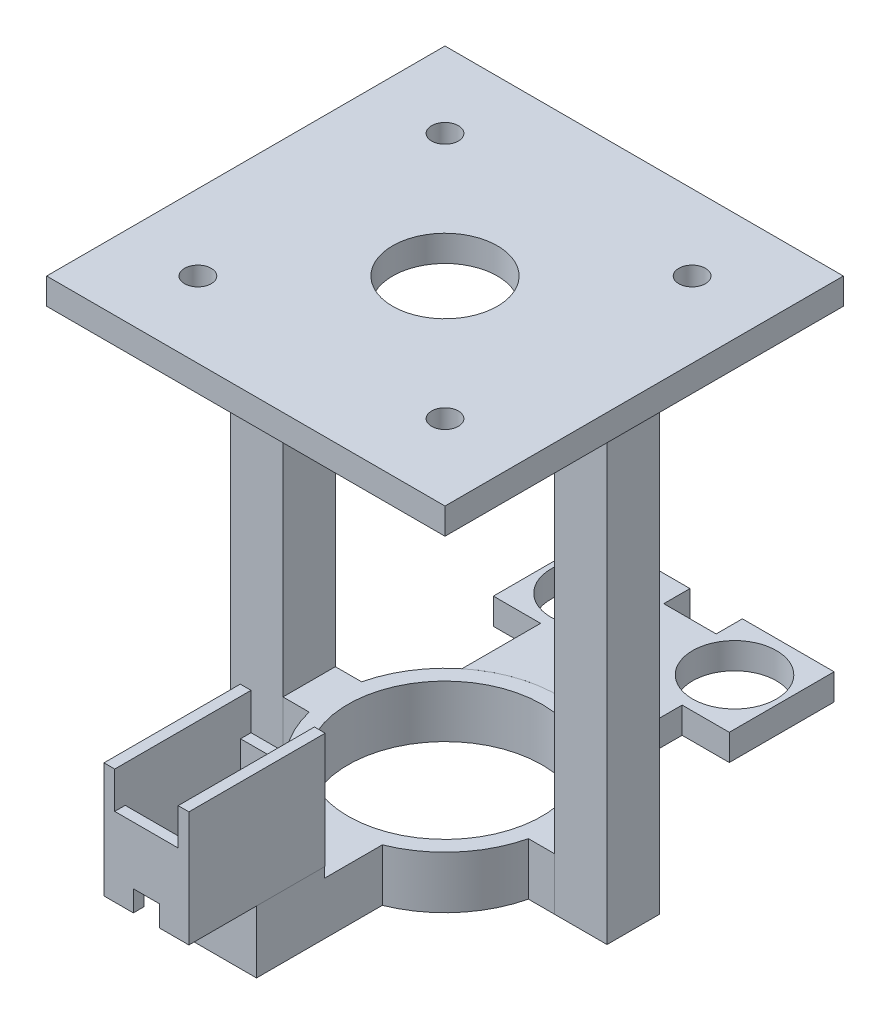
SolidWorks part; units mm, degrees
ref_plane "Front Plane" through (0, 0, 0) normal (0, 0, 1) x (1, 0, 0)
ref_plane "Top Plane" through (0, 0, 0) normal (0, 1, 0) x (1, 0, 0)
ref_plane "Right Plane" through (0, 0, 0) normal (1, 0, 0) x (0, 0, -1)
sketch "Sketch2" plane through (0, 0, 0) normal (0, 1, 0) x (1, 0, 0)
  line L0 (0, 18.5) -> (0, -18.5) construction
  line L1 (-18.5, 0) -> (18.5, 0) construction
  line L2 (0, -5) -> (0, 5) construction
  line L3 (-20.9105, 5) -> (-35.9105, 5)
  line L4 (-35.9105, 5) -> (-35.9105, -5)
  line L5 (-35.9105, -5) -> (-20.9105, -5)
  line L6 (35.9105, -5) -> (20.9105, -5)
  line L7 (35.9105, 5) -> (35.9105, -5)
  line L8 (20.9105, 5) -> (35.9105, 5)
  line L9 (0, 31.7332) -> (22.5, 31.7332)
  line L10 (22.5, 31.7332) -> (22.5, 51.7332)
  line L11 (22.5, 51.7332) -> (5, 51.7332)
  line L12 (-22.5, 51.7332) -> (-22.5, 31.7332)
  line L13 (-22.5, 31.7332) -> (0, 31.7332)
  line L14 (22.5, 41.7332) -> (21.5, 41.7332) construction
  line L20 (-5, 51.7332) -> (-22.5, 51.7332)
  line L21 (0, 46.7332) -> (0, 31.7332) construction
  line L22 (-5, 51.7332) -> (-5, 46.7332)
  line L23 (-5, 46.7332) -> (5, 46.7332)
  line L24 (5, 46.7332) -> (5, 51.7332)
  line L25 (13.5, 49.7332) -> (13.5, 51.7332) construction
  line L26 (13.5, 33.7332) -> (13.5, 31.7332) construction
  line L27 (-13.5, 41.7332) -> (13.5, 41.7332) construction
  line L28 (-13.5, 16.7332) -> (-13.5, 31.7332)
  line L29 (13.5, 31.7332) -> (13.5, 16.7332)
  line L30 (-8, -21.5) -> (8, -21.5) construction
  line L31 (-8, -19.9562) -> (-8, -43.9562)
  line L32 (-8, -43.9562) -> (8, -43.9562)
  line L33 (8, -43.9562) -> (8, -19.9562)
  line L34 (-20.9105, 5) -> (-25.9105, 5) construction
  line L35 (-5.5, -21.5) -> (5.5, -21.5) construction
  line L36 (-25.9105, 5) -> (-25.9105, -5)
  line L37 (25.9105, 5) -> (25.9105, -5)
  circle A0 centre (0, 0) radius 18.5
  circle A1 centre (0, 0) radius 21.5
  circle A2 centre (13.5, 41.7332) radius 8
  circle A3 centre (-13.5, 41.7332) radius 8
  point P9 (0, 0)
  point P45 (0, -21.5)
  point P54 (0, -21.5)
  dimension "D1" = 37
  dimension "D2" = 5
  dimension "D4" = 43
  dimension "D8" = 1
  dimension "D9" = 16
  dimension "D3" = 10
  dimension "D5" = 5
  dimension "D6" = 20
  dimension "D7" = 45
  dimension "D10" = 17.5
  dimension "D11" = 15
  dimension "D12" = 27
  dimension "D13" = 15
  dimension "D14" = 16
  dimension "D15" = 24
  dimension "D16" = 5
extrude "Connector sleeve" add sketch "Sketch2" along normal blind 5 and the other way blind 5 contours A1 A0 | A1 A0 | A1 A0 | A1 A0 region at (-17.6638, 0, -11.1562)
ref_plane "Plane2" through (0, 30, 0) normal (0, 1, 0) x (1, 0, 0)
extrude "Sensor holder" add sketch "Sketch2<10>" along normal blind 5 separate body contours L24 L23 L22 L20 L12 L13 L9 L10 L11 A2 A3 | A1 L29 L9 L13 L28 region at (0, 0, -25.7784) region at (0, 0, -40.8959)
sketch "Sketch2<10>" plane through (0, 0, 0) normal (0, 1, 0) x (1, 0, 0) same geometry as "Sketch2"
extrude "Arms" add sketch "Sketch2<18>" along normal blind 85 from offset 5 contours L36 L3 L4 L5 | L8 L37 L6 L7 region at (-30.9105, 0, 0) region at (30.9105, 0, 0) offset against normal yes
sketch "Sketch2<18>" plane through (0, 0, 0) normal (0, 1, 0) x (1, 0, 0) same geometry as "Sketch2"
extrude "Arms2" add sketch "Sketch2<22>" along normal blind 10 from offset 5 contours A1 L3 L4 L5 | A1 L6 L7 L8 | A1 L3 L36 L5 | A1 L6 L37 L8 region at (-23.6042, 0, 0) region at (-30.9105, 0, 0) region at (23.6042, 0, 0) region at (30.9105, 0, 0) offset against normal yes
sketch "Sketch2<22>" plane through (0, 0, 0) normal (0, 1, 0) x (1, 0, 0) same geometry as "Sketch2"
extrude "Servoholder" add sketch "Sketch2<21>" along normal blind 10 from offset 5 contours A1 L31 L32 L33 region at (0, 0, 32.4701) offset against normal yes
sketch "Sketch2<21>" plane through (0, 0, 0) normal (0, 1, 0) x (1, 0, 0) same geometry as "Sketch2"
sketch "Sketch31" plane through (0, 5, 0) normal (0, 1, 0) x (1, 0, 0)
  line L0 (-8, -43.9562) -> (-8, -30.9562)
  line L1 (-8, -19.9562) -> (-8, -43.9562) construction
  line L2 (-8, -30.9562) -> (8, -30.9562)
  line L3 (8, -43.9562) -> (8, -19.9562) construction
  line L4 (8, -30.9562) -> (8, -43.9562)
  line L5 (8, -43.9562) -> (-8, -43.9562)
  dimension "D1" = 13
extrude "Servoholder2" add sketch "Sketch31" along normal blind 2
sketch "Sketch33" plane through (0, 7, 0) normal (0, 1, 0) x (1, 0, 0)
  line L0 (0, -30.9562) -> (0, -32.9562) construction
  line L1 (8, -30.9562) -> (-8, -30.9562) construction
  line L2 (-8, -43.9562) -> (8, -43.9562) construction
  line L4 (8, -30.9562) -> (-8, -30.9562) construction
  line L6 (-8.1, -30.9562) -> (-8.1, -56.9562)
  line L7 (-8.1, -56.9562) -> (8.1, -56.9562)
  line L8 (8.1, -56.9562) -> (8.1, -30.9562)
  line L9 (0, -43.9562) -> (6.05, -43.9562) construction
  line L10 (0, -56.9562) -> (0, -54.9562) construction
  line L11 (-6.05, -54.9562) -> (6.05, -54.9562)
  line L12 (6.05, -54.9562) -> (6.05, -32.9562)
  line L13 (6.05, -32.9562) -> (-6.05, -32.9562)
  line L14 (-6.05, -54.9562) -> (-6.05, -32.9562)
  line L15 (-8.1, -30.9562) -> (8.1, -30.9562)
  dimension "D1" = 8.1
  dimension "D2" = 26
  dimension "D3" = 6.05
  dimension "D4" = 2
  dimension "D5" = 2
extrude "Servoholder3" add sketch "Sketch33" along normal blind 22
sketch "Servoholder4" plane through (0, 29, 0) normal (0, 1, 0) x (1, 0, 0)
  line L0 (-6.05, -32.9562) -> (-6.05, -30.9562)
  line L1 (8, -30.9562) -> (-8, -30.9562) construction
  line L2 (-6.05, -30.9562) -> (6.05, -30.9562)
  line L3 (8.1, -30.9562) -> (-8.1, -30.9562) construction
  line L4 (6.05, -30.9562) -> (6.05, -32.9562)
  line L5 (6.05, -32.9562) -> (-6.05, -32.9562)
  line L6 (-6.05, -43.9562) -> (6.05, -43.9562) construction
  line L7 (-6.05, -32.9562) -> (-6.05, -54.9562) construction
  line L8 (6.05, -54.9562) -> (6.05, -32.9562) construction
  line L9 (6.05, -56.9562) -> (6.05, -54.9562)
  line L10 (-6.05, -54.9562) -> (-6.05, -56.9562)
  line L11 (-6.05, -56.9562) -> (6.05, -56.9562)
  line L12 (6.05, -54.9562) -> (-6.05, -54.9562)
extrude "Servogrooves" cut sketch "Servoholder4" against normal blind 7
sketch "Sketch36" plane through (0, 0, 56.9562) normal (0, 0, 1) x (1, 0, 0)
  line L0 (0, 7) -> (0, 11) construction
  line L1 (-8.1, 7) -> (8.1, 7) construction
  line L2 (-2.5, 11) -> (2.5, 11)
  line L3 (-2.5, 11) -> (-2.5, 7)
  line L4 (-6.05, 7) -> (6.05, 7) construction
  line L5 (2.5, 11) -> (2.5, 7)
  line L6 (2.5, 7) -> (-2.5, 7)
  point P8 (0, 11)
  dimension "D1" = 4
  dimension "D2" = 2.5
extrude "Servowiring" cut sketch "Sketch36" against normal blind 2
sketch "Sketch4" plane through (0, 80, 0) normal (0, 1, 0) x (1, 0, 0)
  line L1 (-38, -38) -> (38, -38)
  line L2 (-38, -38) -> (-38, 38)
  line L3 (-38, 38) -> (38, 38)
  line L4 (38, -38) -> (38, 38)
  line L5 (-38, -38) -> (38, 38) construction
  line L6 (-38, 38) -> (38, -38) construction
  circle A0 centre (0, 0) radius 10
  point P0 (0, 0)
  dimension "D2" = 20
  dimension "D1" = 76
  dimension "D3" = 76
extrude "Motor enclosure" add sketch "Sketch4" along normal blind 5
sketch "Sketch6" plane through (0, 85, 0) normal (0, 1, 0) x (1, 0, 0)
  line L1 (-23.57, 0) -> (23.57, 0) construction
  line L7 (23.57, -28.2) -> (23.57, -23.57) construction
  line L23 (-28.2, -28.2) -> (28.2, -28.2)
  line L24 (-28.2, -28.2) -> (-28.2, 28.2)
  line L25 (-28.2, 28.2) -> (28.2, 28.2)
  line L27 (28.2, -28.2) -> (28.2, 28.2)
  line L28 (-28.2, -28.2) -> (28.2, 28.2) construction
  line L29 (-28.2, 28.2) -> (28.2, -28.2) construction
  line L30 (23.57, -23.57) -> (28.2, -23.57) construction
  line L31 (0, 28.2) -> (0, -28.2) construction
  circle A0 centre (23.57, -23.57) radius 2.55
  circle A1 centre (-23.57, -23.57) radius 2.55
  circle A2 centre (-23.57, 23.57) radius 2.55
  circle A3 centre (23.57, 23.57) radius 2.55
  point P3 (0, 0)
  point P6 (0, 0)
  point P7 (0, 0)
  point P15 (0, 0)
  point P16 (0, -38)
  point P18 (0, -38)
  dimension "D3" = 5.1
  dimension "D1" = 56.4
  dimension "D2" = 47.14
extrude "Cut-Extrude1" cut sketch "Sketch6" against normal blind 10 contours A1 | A0 | A2 | A3 region at (23.57, 85, 23.57) region at (-23.57, 85, 23.57) region at (-23.57, 85, -23.57)
